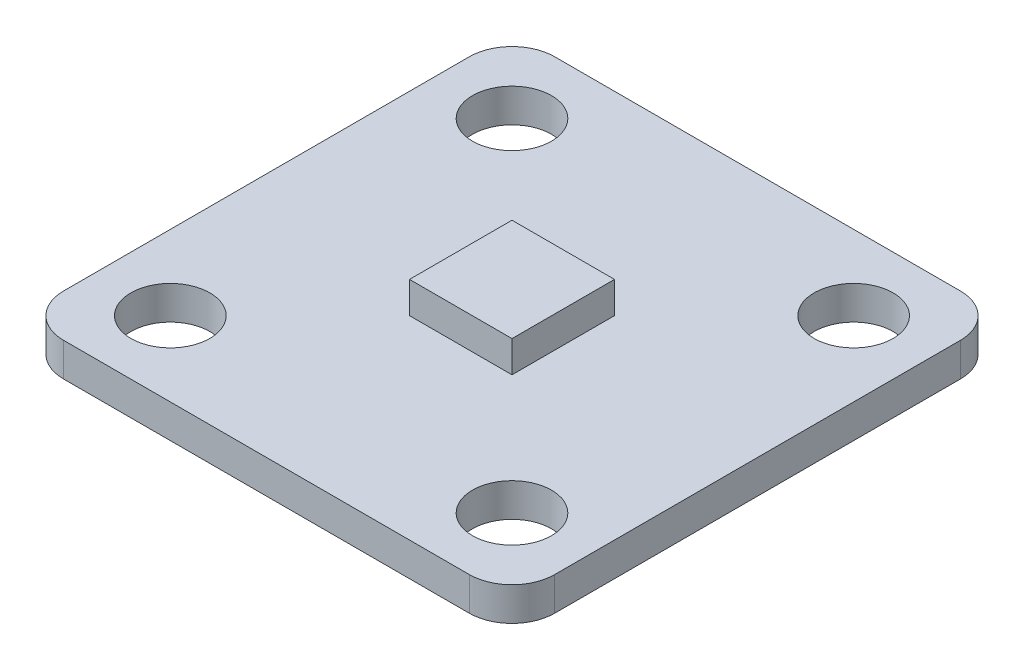
SolidWorks part; units mm, degrees
ref_plane "Front Plane" through (0, 0, 0) normal (0, 0, 1) x (1, 0, 0)
ref_plane "Top Plane" through (0, 0, 0) normal (0, 1, 0) x (1, 0, 0)
ref_plane "Right Plane" through (0, 0, 0) normal (1, 0, 0) x (0, 0, -1)
sketch "Sketch1" plane through (0, 0, 0) normal (0, 1, 0) x (1, 0, 0)
  line L1 (-9.5, -11.5) -> (9.5, -11.5)
  line L2 (-11.5, -9.5) -> (-11.5, 9.5)
  line L3 (-9.5, 11.5) -> (9.5, 11.5)
  line L4 (11.5, -9.5) -> (11.5, 9.5)
  line L5 (-11.5, -11.5) -> (11.5, 11.5) construction
  line L6 (-11.5, 11.5) -> (11.5, -11.5) construction
  line L7 (-8, -8) -> (8, -8) construction
  line L8 (-8, -8) -> (-8, 8) construction
  line L9 (-8, 8) -> (8, 8) construction
  line L10 (8, -8) -> (8, 8) construction
  line L11 (-8, -8) -> (8, 8) construction
  line L12 (-8, 8) -> (8, -8) construction
  line L13 (-2.4, -2.4) -> (2.4, -2.4)
  line L14 (-2.4, -2.4) -> (-2.4, 2.4)
  line L15 (-2.4, 2.4) -> (2.4, 2.4)
  line L16 (2.4, -2.4) -> (2.4, 2.4)
  line L17 (-2.4, -2.4) -> (2.4, 2.4) construction
  line L18 (-2.4, 2.4) -> (2.4, -2.4) construction
  arc A0 (-9.5, -11.5) -> (-11.5, -9.5) centre (-9.5, -9.5) cw
  arc A1 (9.5, -11.5) -> (11.5, -9.5) centre (9.5, -9.5) ccw
  arc A2 (9.5, 11.5) -> (11.5, 9.5) centre (9.5, 9.5) cw
  arc A3 (-11.5, 9.5) -> (-9.5, 11.5) centre (-9.5, 9.5) cw
  circle A4 centre (-8, 8) radius 1.85
  circle A5 centre (8, 8) radius 1.85
  circle A6 centre (8, -8) radius 1.85
  circle A7 centre (-8, -8) radius 1.85
  point P0 (0, 0)
  point P6 (0, 0)
  point P27 (0, 0)
  dimension "D5" = 2
  dimension "D6" = 3.7
  dimension "D1" = 23
  dimension "D2" = 23
  dimension "D3" = 16
  dimension "D4" = 16
  dimension "D7" = 4.8
  dimension "D8" = 4.8
extrude "Boss-Extrude1" add sketch "Sketch1" along normal blind 1.57 contours L13 L16 L15 L14 | A3 L2 A0 L1 A1 L4 A2 L3 A7 A6 A5 A4 L16 L13 L14 L15 region at (-10.6842, 0, 10.6842) region at (0, 0, 0)
sketch "Sketch2" plane through (0, 1.57, 0) normal (0, 1, 0) x (1, 0, 0)
  line L4 (-2.4, -2.4) -> (2.4, -2.4)
  line L5 (2.4, -2.4) -> (2.4, 2.4)
  line L6 (2.4, 2.4) -> (-2.4, 2.4)
  line L7 (-2.4, 2.4) -> (-2.4, -2.4)
  line L8 (-2.4, -2.4) -> (2.4, -2.4)
  line L9 (2.4, -2.4) -> (2.4, 2.4)
  line L10 (2.4, 2.4) -> (-2.4, 2.4)
  line L11 (-2.4, 2.4) -> (-2.4, -2.4)
  line L12 (-11.5, 9.5) -> (-11.5, -9.5)
  line L13 (-9.5, -11.5) -> (9.5, -11.5)
  line L14 (11.5, -9.5) -> (11.5, 9.5)
  line L15 (9.5, 11.5) -> (-9.5, 11.5)
  line L16 (-11.5, 9.5) -> (-11.5, -9.5)
  line L17 (-9.5, -11.5) -> (9.5, -11.5)
  line L18 (11.5, -9.5) -> (11.5, 9.5)
  line L19 (9.5, 11.5) -> (-9.5, 11.5)
  circle A1 centre (8, 8) radius 1.85
  circle A2 centre (8, 8) radius 1.85
  circle A3 centre (-8, -8) radius 1.85
  circle A4 centre (-8, -8) radius 1.85
  circle A5 centre (8, -8) radius 1.85
  circle A6 centre (8, -8) radius 1.85
  circle A7 centre (-8, 8) radius 1.85
  circle A8 centre (-8, 8) radius 1.85
  arc A12 (-11.5, -9.5) -> (-9.5, -11.5) centre (-9.5, -9.5) ccw
  arc A13 (9.5, -11.5) -> (11.5, -9.5) centre (9.5, -9.5) ccw
  arc A14 (11.5, 9.5) -> (9.5, 11.5) centre (9.5, 9.5) ccw
  arc A15 (-9.5, 11.5) -> (-11.5, 9.5) centre (-9.5, 9.5) ccw
  arc A16 (-11.5, -9.5) -> (-9.5, -11.5) centre (-9.5, -9.5) ccw
  arc A17 (9.5, -11.5) -> (11.5, -9.5) centre (9.5, -9.5) ccw
  arc A18 (11.5, 9.5) -> (9.5, 11.5) centre (9.5, 9.5) ccw
  arc A19 (-9.5, 11.5) -> (-11.5, 9.5) centre (-9.5, 9.5) ccw
  dimension "D1" = 0
  dimension "D2" = 0
  dimension "D3" = 0
  dimension "D4" = 0
  dimension "D5" = 0
  dimension "D6" = 0
extrude "Boss-Extrude2" add sketch "Sketch2" along normal blind 1.47 contours L10 L11 L8 L9 region at (0, 1.57, 0)
equation "\"a\"= 1"
equation "\"b\"= 1"
equation "\"c\"= 1"
equation "\"d\"= 1"
equation "\"e\"= 1"
equation "\"x\"= 1"
equation "\"y\"= 1"
equation "\"z\"= 1"
